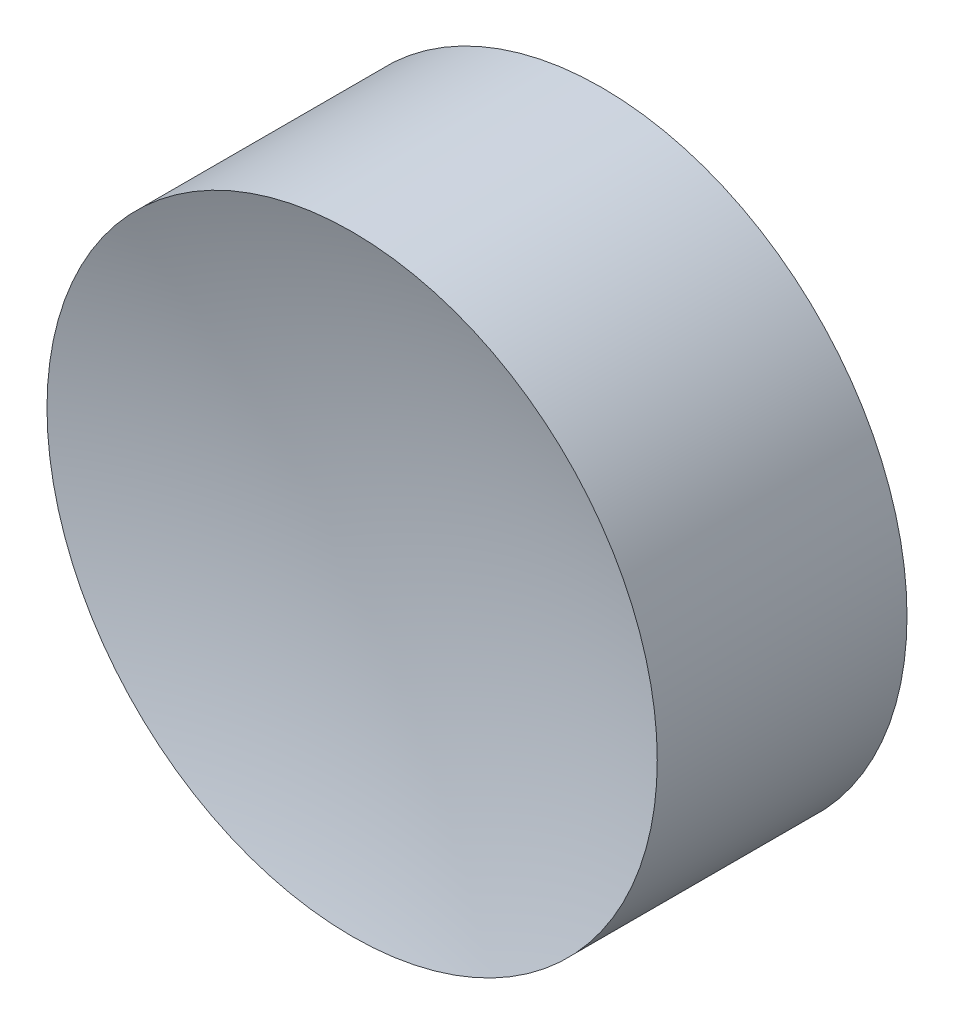
SolidWorks part; units mm, degrees
ref_plane "Ebene vorne" through (0, 0, 0) normal (0, 0, 1) x (1, 0, 0)
ref_plane "Ebene oben" through (0, 0, 0) normal (0, 1, 0) x (1, 0, 0)
ref_plane "Ebene rechts" through (0, 0, 0) normal (1, 0, 0) x (0, 0, -1)
other "Massenmittelpunkt"
sketch "Skizze1" plane through (0, 0, 0) normal (0, 1, 0) x (1, 0, 0)
  line L0 (0, 0.75) -> (0, -0.75)
  line L1 (3, -1.2276) -> (3, 1.2276)
  line L2 (0, 1.2276) -> (0, -1.2276) construction
  arc A0 (3, 1.2276) -> (0, 0.75) centre (0, 10.41) cw
  arc A1 (0, -0.75) -> (3, -1.2276) centre (0, -10.41) cw
revolve "Rotation1" add sketch "Skizze1" angle 360 about L2 reverse direction yes
ref_plane "Ebene1" through (3, 0, 0) normal (1, 0, 0) x (0, 0, -1)
ref_axis "Achse2" through (-3.3, 0, 0) along (1, 0, 0)
ref_point "Punkt1"
ref_axis "SWASI_Opitcal_Axis" through (0, 0, -1.2276) along (0, 0, 1)
ref_plane "Ebene2" through (-3, 0, 0) normal (-1, 0, 0) x (0, 0, 1)
ref_point "Punkt2"
ref_point "Punkt3"
